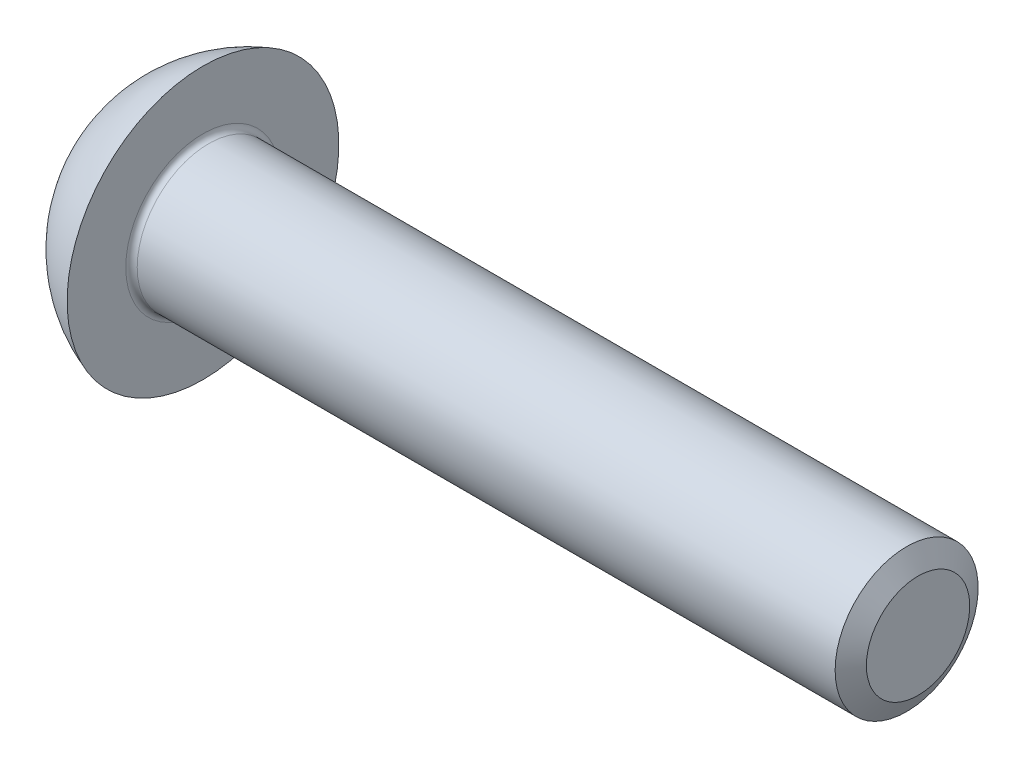
SolidWorks part; units mm, degrees
ref_plane "前视基准面" through (0, 0, 0) normal (0, 0, 1) x (1, 0, 0)
ref_plane "上视基准面" through (0, 0, 0) normal (0, 1, 0) x (1, 0, 0)
ref_plane "右视基准面" through (0, 0, 0) normal (1, 0, 0) x (0, 0, -1)
sketch "草图1" plane through (0, 0, 0) normal (0, 0, 1) x (1, 0, 0)
  line L0 (-27.75, 0) -> (0, 0) construction
  line L1 (0, 2.5) -> (-24.8, 2.5)
  line L2 (-25, 2.7) -> (-25, 4.75)
  line L3 (-27.75, 0) -> (-27.75, 2.5)
  line L4 (0, 2.5) -> (0, 0)
  line L5 (-27.75, 0) -> (0, 0)
  arc A0 (-25, 4.75) -> (-27.75, 2.5) centre (-23.4091, 0) ccw
  arc A1 (-24.8, 2.5) -> (-25, 2.7) centre (-24.8, 2.7) cw
  point P10 (-25, 2.5)
  dimension "r" = 0.2
  dimension "d" = 5
  dimension "dk" = 9.5
  dimension "k" = 2.75
  dimension "l" = 25
revolve "旋转1" add sketch "草图1" angle 360 about L0
cosmetic thread "装饰螺纹线1" parameters "D1"=2, "D2"=4.3
sketch "草图2" plane through (-27.75, 0, 0) normal (-1, 0, 0) x (0, 0, 1)
  line L1 (0, 1.7321) -> (-1.5, 0.866)
  line L2 (-1.5, 0.866) -> (-1.5, -0.866)
  line L3 (-1.5, -0.866) -> (0, -1.7321)
  line L4 (0, -1.7321) -> (1.5, -0.866)
  line L5 (1.5, -0.866) -> (1.5, 0.866)
  line L6 (1.5, 0.866) -> (0, 1.7321)
  circle A0 centre (0, 0) radius 1.5 construction
  dimension "s" = 3
extrude "切除-拉伸1" cut sketch "草图2" against normal blind 2.75
sketch "草图6" plane through (0, 0, 0) normal (0, 0, 1) x (1, 0, 0)
  line L0 (-26.19, 1.7321) -> (-25, 0)
  line L1 (-24.56, 1.7321) -> (-24.56, 0)
  line L2 (-24.56, 1.7321) -> (-26.19, 1.7321)
  line L3 (-27.75, 0) -> (-25, 0) construction
  line L4 (-24.56, 0) -> (-25, 0)
  line L5 (-27.75, 0) -> (-31.19, 0) construction
  dimension "k" = 2.75
  dimension "t" = 1.56
  dimension "e-s" = 0.44
  dimension "e" = 3.44
revolve "旋转2" add sketch "草图6" angle 360 about L3
sketch "草图7" plane through (0, 0, 0) normal (0, 0, 1) x (1, 0, 0)
  line L3 (-27.75, 1.7321) -> (-27.31, 0)
  line L4 (-27.75, 0) -> (-27.31, 0) construction
  line L7 (-27.75, 1.7321) -> (-27.75, 0)
  line L8 (-27.75, 0) -> (-27.31, 0)
  dimension "e-s" = 0.44
revolve "切除-旋转5" cut sketch "草图7" angle 360 about L4
sketch "草图4" plane through (0, 0, 0) normal (0, 0, 1) x (1, 0, 0)
  line L0 (-0.4, 2.5) -> (0, 1.8072)
  line L1 (-0.4, 2.5) -> (0.4, 2.5)
  line L2 (0.4, 2.5) -> (0, 1.8072)
  line L4 (0, -2.5) -> (0, 2.5) construction
  line L5 (-0.4, 0) -> (0.4, 0) construction
  dimension "d" = 2.5
  dimension "p" = 0.8
revolve "切除-旋转1" cut sketch "草图4" angle 360 about L5
ref_axis "基准轴1" through (-8.1887, 0, 0) along (1, 0, 0)
pattern_linear "阵列(线性)1" [suppressed] count 3 spacing 0.8 along (-1, 0, 0) of bodies 104
equation "\"D2@装饰螺纹线1\" = \"d@草图1\" * 0.86"
equation "\"k@草图6\" = \"k@切除-拉伸1\""
equation "\"e-s@草图6\" = \"e@草图6\" - \"s@草图2\""
equation "\"e-s@草图7\" = \"e-s@草图6\""
equation "\"d@草图4\" = \"d@草图1\" / 2"
equation "\"k@切除-拉伸1\" = \"k@草图1\""
equation "\"D1@阵列(线性)1\" = \"D1@装饰螺纹线1\" / \"p@草图4\""
equation "\"D3@阵列(线性)1\" = \"p@草图4\""
